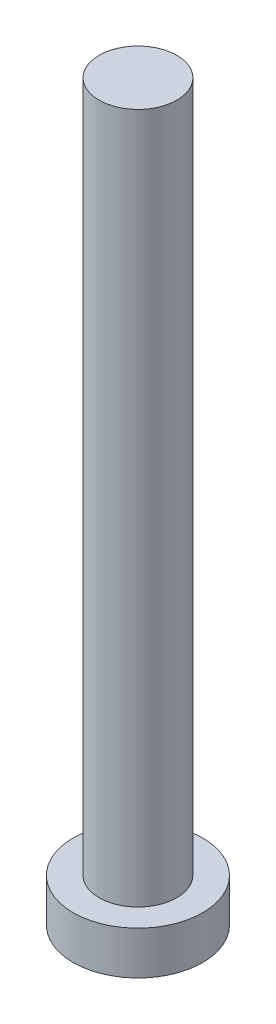
SolidWorks part; units mm, degrees
ref_plane "Front Plane" through (0, 0, 0) normal (0, 0, 1) x (1, 0, 0)
ref_plane "Top Plane" through (0, 0, 0) normal (0, 1, 0) x (1, 0, 0)
ref_plane "Right Plane" through (0, 0, 0) normal (1, 0, 0) x (0, 0, -1)
sketch "Sketch2" plane through (0, 0, 0) normal (0, 1, 0) x (1, 0, 0)
  circle A0 centre (0, 0) radius 0.75
  circle A1 centre (0, 0) radius 0.45
  dimension "D1" = 0.9
  dimension "D2" = 1.5
extrude "Boss-Extrude1" add sketch "Sketch2" along normal blind 8 contours A1
extrude "Boss-Extrude2" add sketch "Sketch2<3>" against normal blind 0.5 contours A0
sketch "Sketch2<3>" plane through (0, 0, 0) normal (0, 1, 0) x (1, 0, 0) same geometry as "Sketch2"
equation "\"pinDia\"= .9mm"
equation "\"headHeight\"= .5mm"
equation "\"headDia\"= 1.5mm"
equation "\"D1@Sketch2\"=\"pinDia\""
equation "\"D2@Sketch2\"=\"headDia\""
equation "\"pinLen\"= 8mm"
equation "\"D1@Boss-Extrude1\"=\"pinLen\""
equation "\"D1@Boss-Extrude2\"=\"headHeight\""
